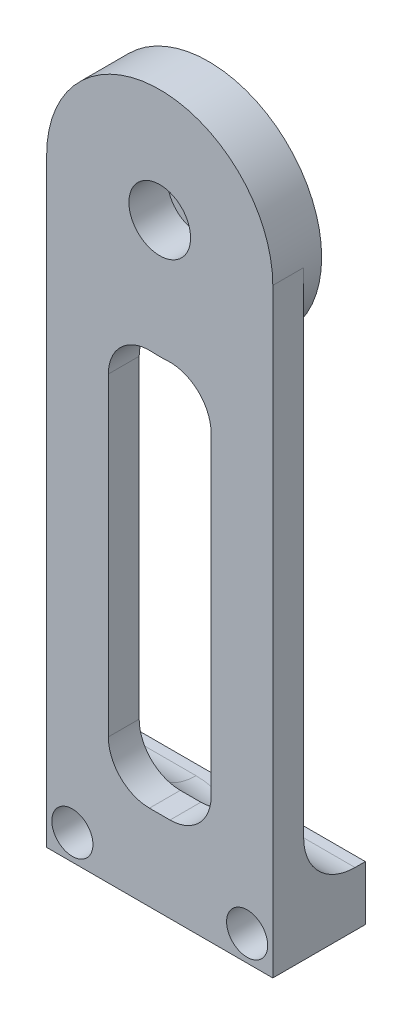
SolidWorks part; units mm, degrees
ref_plane "Front Plane" through (0, 0, 0) normal (0, 0, 1) x (1, 0, 0)
ref_plane "Top Plane" through (0, 0, 0) normal (0, 1, 0) x (1, 0, 0)
ref_plane "Right Plane" through (0, 0, 0) normal (1, 0, 0) x (0, 0, -1)
sketch "Sketch1" plane through (0, 0, 0) normal (0, 0, 1) x (1, 0, 0)
  line L0 (0, 29.175) -> (0, -29.175) construction
  line L1 (-11, 29.175) -> (-11, -29.175)
  line L2 (11, 29.175) -> (11, -29.175)
  line L3 (-11, -29.175) -> (11, -29.175)
  line L5 (-11, -29.175) -> (11, -29.175)
  line L6 (-11, -29.175) -> (-11, -23.865)
  line L7 (-11, -23.865) -> (11, -23.865)
  line L8 (11, -29.175) -> (11, -23.865)
  line L10 (-5, 18.8188) -> (-5, -20.865)
  line L11 (-5, -20.865) -> (5, -20.865)
  line L12 (5, 18.8188) -> (5, -20.865)
  circle A0 centre (0, 29.175) radius 11
  arc A2 (-5, 18.8188) -> (5, 18.8188) centre (0, 29.175) ccw
  point P8 (0, 0)
  dimension "D2" = 22
  dimension "D6" = 6
  dimension "D7" = 11.5
  dimension "D1" = 58.35
  dimension "D3" = 5.31
  dimension "D4" = 3
  dimension "D5" = 6
extrude "Boss-Extrude1" add sketch "Sketch1" along normal blind 3 contours A0 | L0 A0 L1 | A0 L0 L2 | L6 L5 L8 L7 region at (0, 18.1176, 0) region at (0, 29.175, 0)
extrude "Boss-Extrude2" add sketch "Sketch1<3>" against normal blind 1.75 contours A0 region at (0, 29.175, 0)
sketch "Sketch1<3>" plane through (0, 0, 0) normal (0, 0, 1) x (1, 0, 0) same geometry as "Sketch1"
sketch "Sketch2" plane through (0, 0, 3) normal (0, 0, 1) x (1, 0, 0)
  circle A0 centre (0, 29.175) radius 1.75
  circle A3 centre (0, 29.175) radius 3
  dimension "D1" = 3.5
  dimension "D2" = 6
extrude "Cut-Extrude1" cut sketch "Sketch2" against normal up to surface (4.75 mm away) contours A0 region at (0, 29.175, 3) up to face at (11, 29.175, -1.75)
extrude "Cut-Extrude2" cut sketch "Sketch2<3>" against normal offset from surface (3.75 mm away) 1 contours A3 A0 region at (-2.9151, 29.175, 3) up to face at (1.75, 29.175, -1.75)
sketch "Sketch2<3>" plane through (0, 0, 3) normal (0, 0, 1) x (1, 0, 0) same geometry as "Sketch2"
extrude "Boss-Extrude3" add sketch "Sketch1<6>" against normal blind 6 contours L7 L0 L5 L2 | L0 L7 L1 L3 region at (-5.5, -26.52, 0) region at (5.5, -26.52, 0)
sketch "Sketch1<6>" plane through (0, 0, 0) normal (0, 0, 1) x (1, 0, 0) same geometry as "Sketch1"
sketch "Sketch3" plane through (0, 0, 3) normal (0, 0, 1) x (1, 0, 0)
  line L1 (-8.5, -26.68) -> (8.5, -26.68) construction
  line L2 (-11, -29.175) -> (11, -29.175) construction
  circle A1 centre (-8.5, -26.68) radius 1.1
  circle A2 centre (8.5, -26.68) radius 1.1
  circle A3 centre (-8.5, -26.68) radius 2
  circle A4 centre (8.5, -26.68) radius 2
  point P5 (0, -26.68)
  dimension "D2" = 2.2
  dimension "D3" = 4
  dimension "D4" = 2.495
  dimension "D1" = 17
extrude "Cut-Extrude3" cut sketch "Sketch3" against normal up to surface (9 mm away) contours A1 | A2 region at (-8.5, -26.68, 3) up to face at (0, -26.52, -6)
extrude "Cut-Extrude4" cut sketch "Sketch3<3>" against normal offset from surface (8 mm away) 1 up to face at (-7.4, -26.68, -6)
sketch "Sketch3<3>" plane through (0, 0, 3) normal (0, 0, 1) x (1, 0, 0) same geometry as "Sketch3"
fillet "Filete1" radius 4 4 edges at (5, 18.8188, 1.5) (-5, 18.8188, 1.5) (5, -20.865, 1.5) (-5, -20.865, 1.5)
fillet "Filete2" radius 5 1 edges at (0, -23.865, 0)
